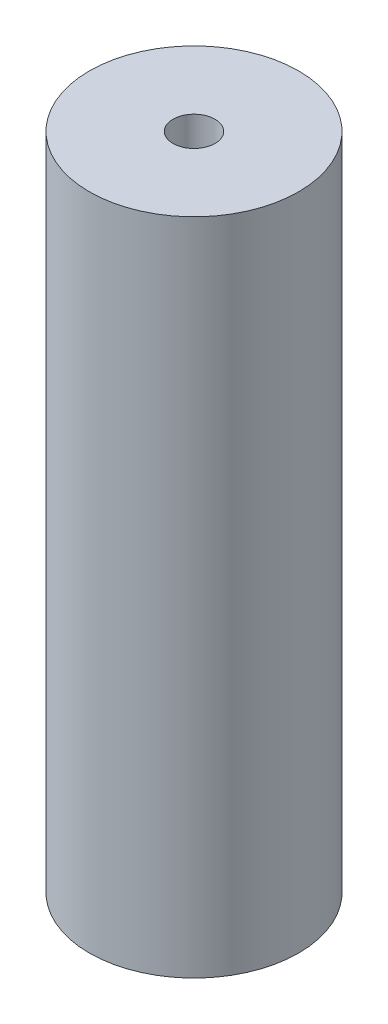
SolidWorks part; units mm, degrees
material "Delrin 2700 NC010, Low Viscosity Acetal Copolymer (SS)"
ref_plane "Front Plane" through (0, 0, 0) normal (0, 0, 1) x (1, 0, 0)
ref_plane "Top Plane" through (0, 0, 0) normal (0, 1, 0) x (1, 0, 0)
ref_plane "Right Plane" through (0, 0, 0) normal (1, 0, 0) x (0, 0, -1)
sketch "Sketch1" plane through (0, 0, 0) normal (0, 1, 0) x (1, 0, 0)
  circle A0 centre (0, 0) radius 12.7
  dimension "D1" = 25.4
extrude "Boss-Extrude1" add sketch "Sketch1" along normal blind 80
sketch "Sketch2" plane through (0, 0, 0) normal (0, -1, 0) x (1, 0, 0)
  point P0 (0, 0)
hole_wizard "Tap Drill for 1/4-20 Tap1" positions "Sketch2" profile "Sketch3" hole size "1/4-20" standard "ANSI Inch"
sketch "Sketch3" plane through (0, 0, 0) normal (1, 0, 0) x (0, 0, -1)
  line L0 (0, 0) -> (0, 11.6938)
  line L1 (0, 11.6938) -> (2.5527, 10.16)
  line L2 (2.5527, 10.16) -> (2.5527, 0)
  line L5 (2.5527, 0) -> (0, 0)
  line L10 (0, 11.6938) -> (-2.5527, 10.16) construction
  line L11 (0, -6.35) -> (0, 107.95) construction
  dimension "Hole Dia." = 5.1054
  dimension "Hole Depth" = 10.16
  dimension "Drill Angle" = 118
sketch "Sketch4" plane through (0, 80, 0) normal (0, 1, 0) x (1, 0, 0)
  point P0 (0, 0)
hole_wizard "Tap Drill for 1/4-20 Tap2" positions "Sketch4" profile "Sketch5" hole size "1/4-20" standard "ANSI Inch"
sketch "Sketch5" plane through (0, 80, 0) normal (1, 0, 0) x (0, 0, 1)
  line L0 (0, 0) -> (0, 11.6938)
  line L1 (0, 11.6938) -> (2.5527, 10.16)
  line L2 (2.5527, 10.16) -> (2.5527, 0)
  line L5 (2.5527, 0) -> (0, 0)
  line L10 (0, 11.6938) -> (-2.5527, 10.16) construction
  line L11 (0, -6.35) -> (0, 107.95) construction
  dimension "Hole Dia." = 5.1054
  dimension "Hole Depth" = 10.16
  dimension "Drill Angle" = 118
